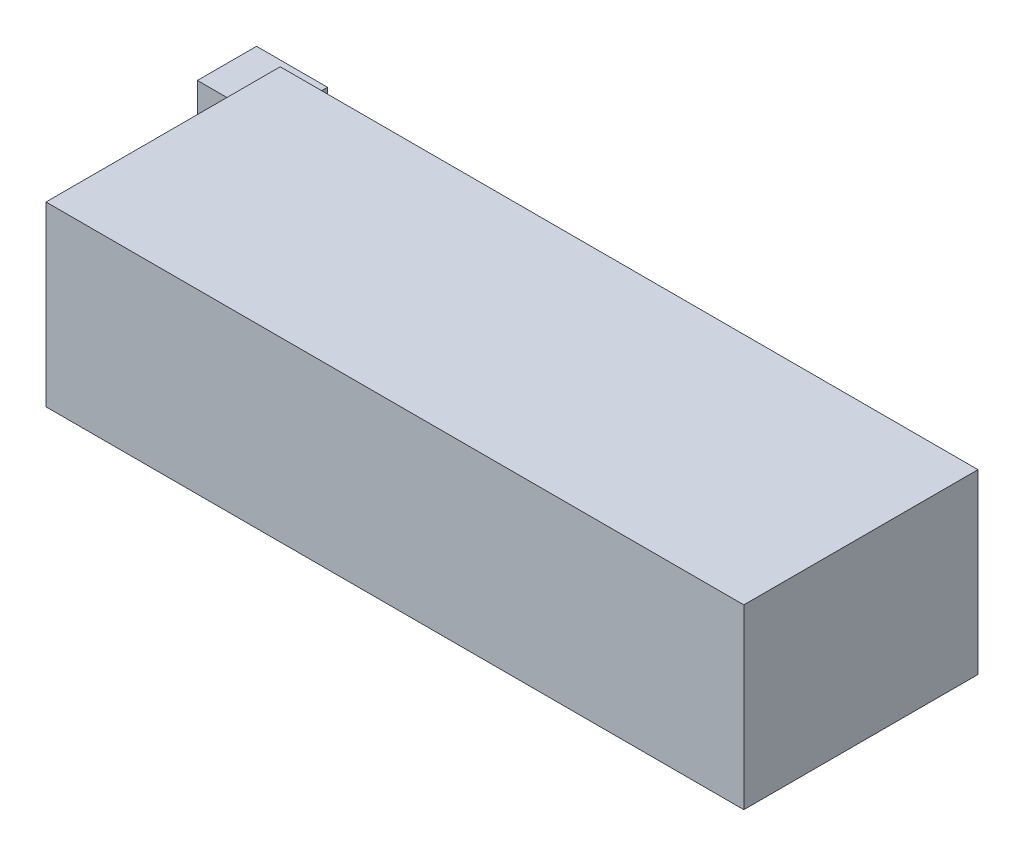
SolidWorks part; units mm, degrees
ref_plane "Front Plane" through (0, 0, 0) normal (0, 0, 1) x (1, 0, 0)
ref_plane "Top Plane" through (0, 0, 0) normal (0, 1, 0) x (1, 0, 0)
ref_plane "Right Plane" through (0, 0, 0) normal (1, 0, 0) x (0, 0, -1)
sketch "Sketch1" plane through (0, 0, 0) normal (0, 1, 0) x (1, 0, 0)
  line L1 (0, 0) -> (74.93, 0)
  line L2 (0, 0) -> (0, -25.146)
  line L3 (0, -25.146) -> (74.93, -25.146)
  line L4 (74.93, 0) -> (74.93, -25.146)
  dimension "D1" = 74.93
  dimension "D2" = 25.146
extrude "Boss-Extrude1" add sketch "Sketch1" along normal blind 19.05
sketch "Sketch2" plane through (0, 0, 0) normal (-1, 0, 0) x (0, 0, 1)
  line L0 (0, 19.05) -> (0, 0) construction
  line L1 (0, 14.605) -> (1.27, 14.605)
  line L2 (0, 14.605) -> (0, 4.445)
  line L3 (0, 4.445) -> (1.27, 4.445)
  line L4 (1.27, 14.605) -> (1.27, 4.445)
  line L5 (3.34, 19.05) -> (3.34, 14.605) construction
  line L6 (0, 19.05) -> (25.146, 19.05) construction
  line L7 (3.34, 4.445) -> (3.34, 0) construction
  line L8 (0, 0) -> (25.146, 0) construction
  line L10 (0, 14.605) -> (-5.08, 14.605)
  line L11 (0, 14.605) -> (0, 4.445)
  line L12 (0, 4.445) -> (-5.08, 4.445)
  line L13 (-5.08, 14.605) -> (-5.08, 4.445)
  line M4 (0, 19.05) -> (0, 0)
  dimension "D1" = 10.16
  dimension "D2" = 5.08
  dimension "D3" = 1.27
extrude "Boss-Extrude2" add sketch "Sketch2" along normal blind 7.62 contours L10 L13 L12 M4 | L4 L1 L3 M4 region at (0, 9.525, 0.635) region at (0, 9.525, -2.54)
fillet "Fillet1" radius 2.54 2 edges at (0, 9.525, 1.27) (0, 9.525, 0)
